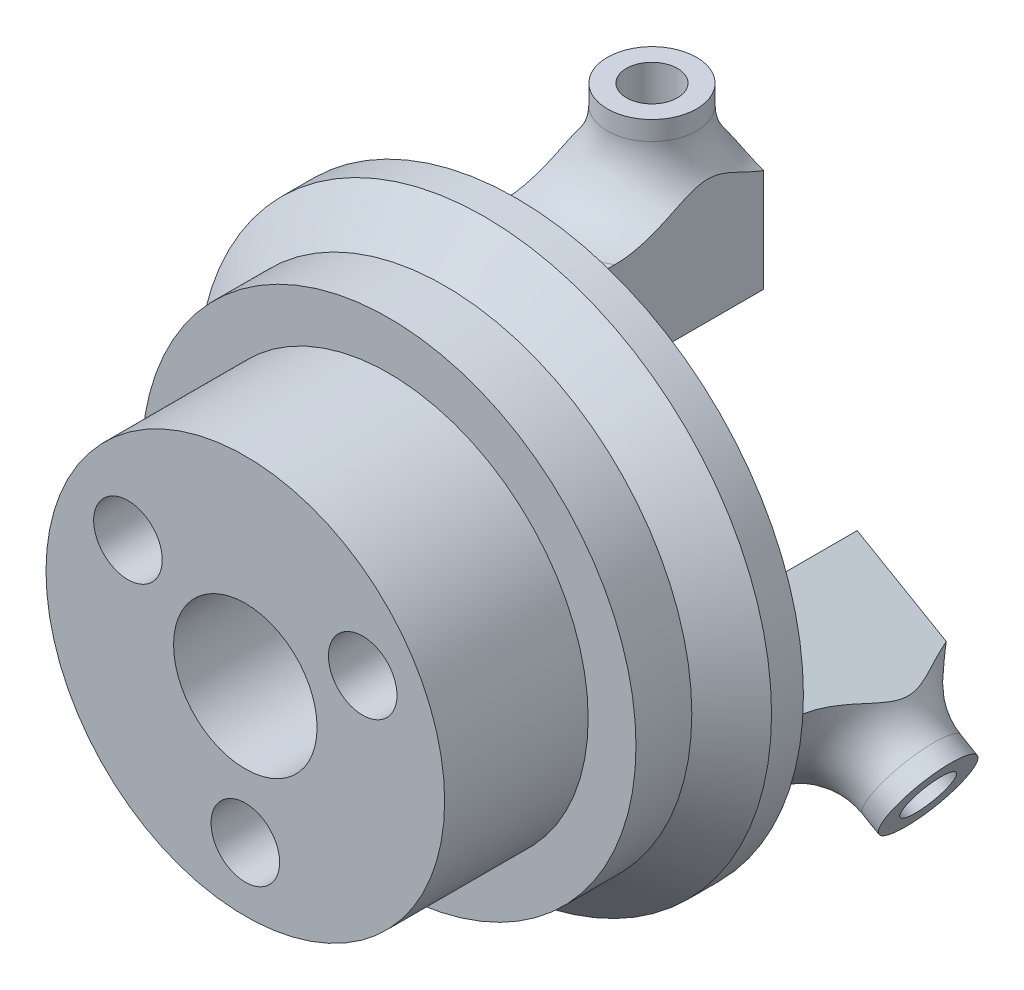
SolidWorks part; units mm, degrees
material "PE Low/Medium Density"
ref_plane "Front Plane" through (0, 0, 0) normal (0, 0, 1) x (1, 0, 0)
ref_plane "Top Plane" through (0, 0, 0) normal (0, 1, 0) x (1, 0, 0)
ref_plane "Right Plane" through (0, 0, 0) normal (1, 0, 0) x (0, 0, -1)
sketch "Sketch1" plane through (0, 0, 0) normal (0, 0, 1) x (1, 0, 0)
  circle A0 centre (0, 0) radius 18
  circle A1 centre (0, 0) radius 4
  dimension "D1" = 36
  dimension "D2" = 8
extrude "Boss-Extrude1" add sketch "Sketch1" along normal mid plane 5
sketch "Sketch5" plane through (0, 0, -2.5) normal (0, 0, 1) x (1, 0, 0)
  circle A0 centre (0, 0) radius 4
  circle A1 centre (0, 0) radius 4 construction
  circle A2 centre (0, 0) radius 7.5
  dimension "D1" = 15
extrude "Boss-Extrude3" add sketch "Sketch5" along normal blind 1
sketch "Sketch8" plane through (0, 0, 2.5) normal (0, 0, 1) x (1, 0, 0)
  circle A0 centre (0, 0) radius 4.5
  circle A1 centre (0, 0) radius 12.5
  dimension "D1" = 25
  dimension "D2" = 9
extrude "Boss-Extrude5" add sketch "Sketch8" along normal blind 12 contours A0 | A1
sketch "Sketch9" plane through (0, 0, 2.5) normal (0, 0, 1) x (1, 0, 0)
  circle A0 centre (0, 0) radius 12.5
  circle A1 centre (0, 0) radius 15.5
  circle A2 centre (0, 0) radius 12.5 construction
  dimension "D1" = 3
extrude "Boss-Extrude6" add sketch "Sketch9" along normal blind 3
hole_wizard "M4 Clearance Hole1" positions "Sketch12" profile "Sketch13" hole size "M4" standard "ANSI Metric" end condition through all
sketch "Sketch12" plane through (0, 0, 14.5) normal (0, 0, 1) x (1, 0, 0)
  line L2 (-7.3612, 4.25) -> (0, 0) construction
  line L3 (0, 0) -> (0, -8.5) construction
  line L4 (0, 8.5) -> (0, 12.5) construction
  line L6 (0, 8.5) -> (0, 4.5) construction
  line L7 (0, 0) -> (7.3612, 4.25) construction
  circle A0 centre (0, 0) radius 8.5 construction
  circle A4 centre (0, 0) radius 12.5 construction
  circle A5 centre (0, 0) radius 12.5 construction
  circle A6 centre (0, 0) radius 4.5 construction
  point P0 (7.3612, 4.25)
  point P2 (-7.3612, 4.25)
  point P4 (0, -8.5)
  dimension "D1" = 60
  dimension "D2" = 120
  dimension "D3" = 120
sketch "Sketch13" plane through (7.3612, 4.25, 14.5) normal (1, 0, 0) x (0, -1, 0)
  line L0 (0, 0) -> (0, 17)
  line L1 (0, 17) -> (2.15, 17)
  line L2 (2.15, 17) -> (2.15, 0)
  line L5 (2.15, 0) -> (0, 0)
  line L11 (0, -6.35) -> (0, 107.95) construction
  dimension "Thru Hole Dia." = 4.3
  dimension "Thru Hole Depth" = 17
sketch "Sketch14" plane through (0, 0, -2.5) normal (0, 0, -1) x (-1, 0, 0)
  line L0 (-11.6913, 4.25) -> (-9.5263, 8)
  line L1 (-9.5263, 8) -> (-5.1962, 8)
  line L2 (-5.1962, 8) -> (-3.0311, 4.25)
  line L3 (-3.0311, 4.25) -> (-5.1962, 0.5)
  line L4 (-5.1962, 0.5) -> (-9.5263, 0.5)
  line L5 (-9.5263, 0.5) -> (-11.6913, 4.25)
  circle A0 centre (-7.3612, 4.25) radius 3.75 construction
  dimension "D1" = 7.5
extrude "Cut-Extrude2" cut sketch "Sketch14" against normal blind 2
pattern_circular "CirPattern2" count 3 over 360 about axis through (0, 0, 2.5) along (0, 0, -1) of "Cut-Extrude2" reverse direction yes
sketch "Sketch15" plane through (0, 0, -2.5) normal (0, 0, -1) x (-1, 0, 0)
  line L0 (0, 0) -> (0, 11.8) construction
  line L1 (-3.5, 8.8) -> (3.5, 8.8)
  line L2 (-3.5, 8.8) -> (-3.5, 14.8)
  line L3 (-3.5, 14.8) -> (3.5, 14.8)
  line L4 (3.5, 8.8) -> (3.5, 14.8)
  line L5 (-3.5, 8.8) -> (3.5, 14.8) construction
  line L6 (-3.5, 14.8) -> (3.5, 8.8) construction
  point P0 (0, 11.8)
  dimension "D1" = 14.8
  dimension "D2" = 6
  dimension "D3" = 7
extrude "Boss-Extrude7" add sketch "Sketch15" along normal blind 12
sketch "Sketch16" plane through (0, 14.8, 0) normal (0, 1, 0) x (1, 0, 0)
  line L0 (0, 11) -> (0, 0) construction
  circle A0 centre (0, 11) radius 2.8
  dimension "D1" = 5.6
  dimension "D2" = 11
extrude "Boss-Extrude8" add sketch "Sketch16" along normal blind 5.2
sketch "Sketch17" plane through (0, 20, 0) normal (0, 1, 0) x (1, 0, 0)
  circle A0 centre (0, 11) radius 1.6
  circle A1 centre (0, 11) radius 2.8 construction
  dimension "D1" = 3.2
extrude "Cut-Extrude3" cut sketch "Sketch17" against normal blind 9
ref_plane "Plane1" through (0, 18.55, 0) normal (0, 1, 0) x (1, 0, 0)
chamfer "Chamfer1" distance 3 angle 45 1 edges at (18, 0, 2.5)
sketch "Sketch18" plane through (0, 8.8, 0) normal (0, -1, 0) x (1, 0, 0)
  line L0 (-2.85, -9.3546) -> (0, -7.7091)
  line L1 (0, -7.7091) -> (2.85, -9.3546)
  line L2 (2.85, -9.3546) -> (2.85, -12.6454)
  line L3 (2.85, -12.6454) -> (0, -14.2909)
  line L4 (0, -14.2909) -> (-2.85, -12.6454)
  line L5 (-2.85, -12.6454) -> (-2.85, -9.3546)
  circle A0 centre (0, -11) radius 2.85 construction
  dimension "D1" = 5.7
extrude "Cut-Extrude5" cut sketch "Sketch18" against normal blind 2.85
fillet "Fillet3" radius 4 1 edges at (0, 14.8, -13.8)
fillet "Fillet5" radius 1 3 edges at (0, 8.8, -2.5) (3.5, 11.8, -2.5) (-3.5, 11.8, -2.5)
pattern_circular "CirPattern4" count 3 over 360 about axis through (0, 0, 2.5) along (0, 0, -1) of "Boss-Extrude7", "Boss-Extrude8", "Cut-Extrude3", "Cut-Extrude5", "Fillet3", "Fillet5"
sketch "Sketch19" plane through (0, 0, -2.5) normal (0, 0, -1) x (-1, 0, 0)
  circle A0 centre (0, 0) radius 4.5
extrude "Cut-Extrude6" cut sketch "Sketch19" against normal blind 25
